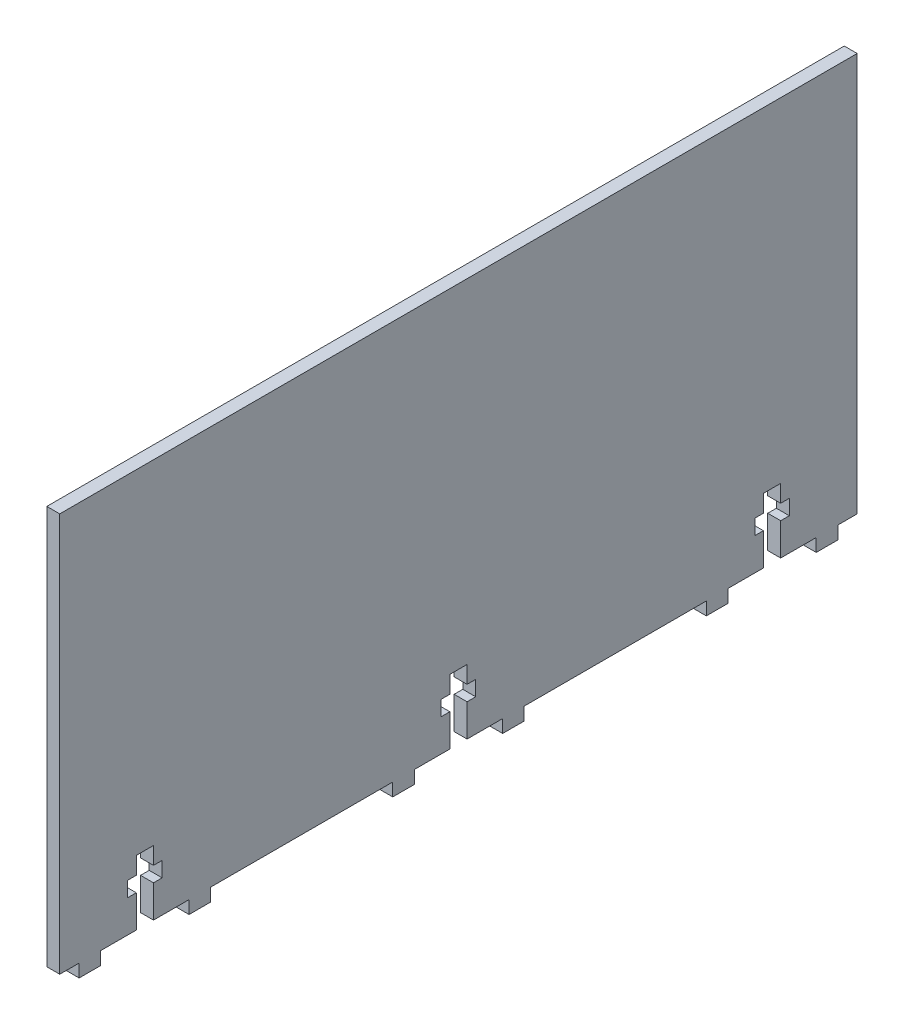
SolidWorks part; units mm, degrees
ref_plane "Front Plane" through (0, 0, 0) normal (0, 0, 1) x (1, 0, 0)
ref_plane "Top Plane" through (0, 0, 0) normal (0, 1, 0) x (1, 0, 0)
ref_plane "Right Plane" through (0, 0, 0) normal (1, 0, 0) x (0, 0, -1)
sketch "Sketch1" plane through (0, 0, 0) normal (1, 0, 0) x (0, 0, -1)
  line L0 (-185, -92.5) -> (185, 92.5) construction
  line L1 (-185, 92.5) -> (185, 92.5)
  line L2 (-185, 92.5) -> (-185, -92.5)
  line L3 (-185, -92.5) -> (-176, -92.5)
  line L4 (185, 92.5) -> (185, -92.5)
  line L5 (0, 92.5) -> (0, -92.5) construction
  line L6 (149.5, -92.5) -> (149.5, -77.5)
  line L7 (149.5, -77.5) -> (153.5, -77.5)
  line L8 (153.5, -77.5) -> (153.5, -70.5)
  line L9 (153.5, -70.5) -> (149.5, -70.5)
  line L10 (149.5, -70.5) -> (149.5, -62.5)
  line L11 (149.5, -62.5) -> (141.5, -62.5)
  line L12 (141.5, -62.5) -> (141.5, -70.5)
  line L13 (141.5, -70.5) -> (137.5, -70.5)
  line L14 (137.5, -70.5) -> (137.5, -77.5)
  line L15 (137.5, -77.5) -> (141.5, -77.5)
  line L16 (141.5, -77.5) -> (141.5, -92.5)
  line L17 (166, -92.5) -> (166, -98.5)
  line L18 (166, -98.5) -> (176, -98.5)
  line L19 (176, -98.5) -> (176, -92.5)
  line L20 (115, -92.5) -> (115, -98.5)
  line L21 (115, -98.5) -> (125, -98.5)
  line L22 (125, -98.5) -> (125, -92.5)
  line L23 (30.5, -92.5) -> (30.5, -98.5)
  line L24 (30.5, -98.5) -> (20.5, -98.5)
  line L25 (20.5, -98.5) -> (20.5, -92.5)
  line L26 (-20.5, -92.5) -> (-20.5, -98.5)
  line L27 (-20.5, -98.5) -> (-30.5, -98.5)
  line L28 (-30.5, -98.5) -> (-30.5, -92.5)
  line L29 (-115, -92.5) -> (-115, -98.5)
  line L30 (-115, -98.5) -> (-125, -98.5)
  line L31 (-125, -98.5) -> (-125, -92.5)
  line L32 (-176, -92.5) -> (-176, -98.5)
  line L33 (-176, -98.5) -> (-166, -98.5)
  line L34 (-166, -98.5) -> (-166, -92.5)
  line L35 (166, -95.5) -> (125, -95.5) construction
  line L36 (115, -95.5) -> (30.5, -95.5) construction
  line L37 (20.5, -95.5) -> (-20.5, -95.5) construction
  line L38 (-30.5, -95.5) -> (-115, -95.5) construction
  line L39 (-125, -95.5) -> (-166, -95.5) construction
  line L40 (-166, -92.5) -> (-125, -92.5)
  line L41 (-115, -92.5) -> (-30.5, -92.5)
  line L42 (-20.5, -92.5) -> (20.5, -92.5)
  line L43 (30.5, -92.5) -> (115, -92.5)
  line L44 (125, -92.5) -> (166, -92.5)
  line L45 (145.5, -62.5) -> (145.5, -92.5) construction
  line L46 (176, -92.5) -> (185, -92.5)
  line L47 (72.75, -92.5) -> (72.75, 92.5) construction
  line L48 (-4, -92.5) -> (-4, -77.5)
  line L49 (-4, -77.5) -> (-8, -77.5)
  line L50 (-8, -77.5) -> (-8, -70.5)
  line L51 (-8, -70.5) -> (-4, -70.5)
  line L52 (-4, -70.5) -> (-4, -62.5)
  line L53 (-4, -62.5) -> (4, -62.5)
  line L54 (4, -62.5) -> (4, -70.5)
  line L55 (4, -70.5) -> (8, -70.5)
  line L56 (8, -70.5) -> (8, -77.5)
  line L57 (8, -77.5) -> (4, -77.5)
  line L58 (4, -77.5) -> (4, -92.5)
  line L59 (-149.5, -92.5) -> (-149.5, -77.5)
  line L60 (-149.5, -77.5) -> (-153.5, -77.5)
  line L61 (-153.5, -77.5) -> (-153.5, -70.5)
  line L62 (-153.5, -70.5) -> (-149.5, -70.5)
  line L63 (-149.5, -70.5) -> (-149.5, -62.5)
  line L64 (-149.5, -62.5) -> (-141.5, -62.5)
  line L65 (-141.5, -62.5) -> (-141.5, -70.5)
  line L66 (-141.5, -70.5) -> (-137.5, -70.5)
  line L67 (-137.5, -70.5) -> (-137.5, -77.5)
  line L68 (-141.5, -77.5) -> (-141.5, -92.5)
  line L69 (-137.5, -77.5) -> (-141.5, -77.5)
  dimension "D1" = 370
  dimension "D2" = 185
  dimension "D3" = 8
  dimension "D4" = 8
  dimension "D5" = 7
  dimension "D6" = 15
  dimension "D7" = 4
  dimension "D8" = 10
  dimension "D9" = 6
  dimension "D10" = 9
  dimension "D11" = 84.5
  dimension "D12" = 41
extrude "Boss-Extrude1" add sketch "Sketch1" along normal mid plane 6 contours L67 L69 L68 L40 L31 L30 L29 L41 L28 L27 L26 L42 L48 L49 L50 L51 L52 L53 L54 L55 L56 L57 L58 L25 L24 L23 L43 L20 L21 L22 L44 L16 L15 L14 L13 L12 L11 L10 L9 L8 L7 L6 L17 L18 L19 L46 L4 L1 L2 region at (0, 0.4984, 0)
